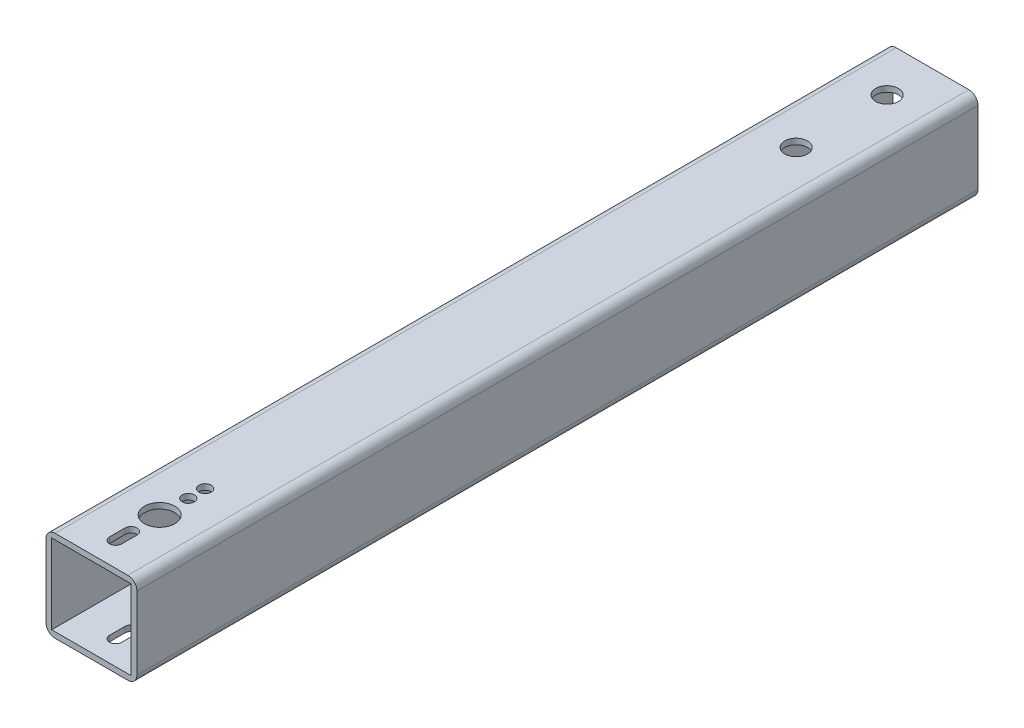
SolidWorks part; units mm, degrees
ref_plane "Front Plane" through (0, 0, 0) normal (0, 0, 1) x (1, 0, 0)
ref_plane "Top Plane" through (0, 0, 0) normal (0, 1, 0) x (1, 0, 0)
ref_plane "Right Plane" through (0, 0, 0) normal (1, 0, 0) x (0, 0, -1)
sketch "Sketch1" plane through (0, 0, 0) normal (0, 0, 1) x (1, 0, 0)
  line L1 (-24.2596, 11.4248) -> (1.1404, 11.4248)
  line L2 (-24.2596, 11.4248) -> (-24.2596, -13.9752)
  line L3 (-24.2596, -13.9752) -> (1.1404, -13.9752)
  line L4 (1.1404, 11.4248) -> (1.1404, -13.9752)
  line L5 (-22.6721, 9.8373) -> (-0.4471, 9.8373)
  line L6 (-22.6721, 9.8373) -> (-22.6721, -12.3877)
  line L7 (-22.6721, -12.3877) -> (-0.4471, -12.3877)
  line L8 (-0.4471, 9.8373) -> (-0.4471, -12.3877)
  dimension "D1" = 25.4
  dimension "D2" = 25.4
  dimension "D3" = 1.5875
  dimension "D4" = 1.5875
  dimension "D5" = 1.5875
  dimension "D6" = 1.5875
extrude "Boss-Extrude1" add sketch "Sketch1" along normal blind 234.95
fillet "Fillet1" radius 2.54 4 edges at (1.1404, -13.9752, 117.475) (-24.2596, -13.9752, 117.475) (-24.2596, 11.4248, 117.475) (1.1404, 11.4248, 117.475)
sketch "Sketch2" plane through (0, 11.4248, 0) normal (0, 1, 0) x (1, 0, 0)
  line L0 (-1.3996, 0) -> (-21.7196, 0) construction
  line L1 (0, 0) -> (0, -59.7417) construction
  line L2 (-11.5596, -12.7) -> (-11.5596, 0) construction
  line L3 (-1.3996, -234.95) -> (-1.3996, 0) construction
  line L4 (-21.7196, -50.8) -> (29.3119, -50.8) construction
  line L5 (-21.7196, 0) -> (-21.7196, -234.95) construction
  circle A0 centre (-11.5596, -12.7) radius 3.175
  circle A2 centre (-11.5596, -38.1) radius 3.175
  dimension "D1" = 6.35
  dimension "D2" = 12.7
  dimension "D3" = 6.35
  dimension "D4" = 50.8
  dimension "D6" = 25.4
extrude "Cut-Extrude1" cut sketch "Sketch2" against normal through all
sketch "Sketch3" plane through (0, 11.4248, 0) normal (0, 1, 0) x (1, 0, 0)
  line L0 (-11.5596, -215.9) -> (-15.3182, -190.7796) construction
  line L1 (-11.5596, -215.9) -> (13.426, -212.1616) construction
  line L2 (-11.5596, -215.9) -> (-29.2422, -202.8202) construction
  line L3 (-11.5596, -215.9) -> (-11.5596, -196.7728) construction
  line L5 (-11.5596, -223.9) -> (-11.5596, -228.195) construction
  line L6 (-9.8596, -223.9) -> (-9.8596, -228.195)
  line L7 (-13.2596, -223.9) -> (-13.2596, -228.195)
  line L8 (-11.5596, -207.9) -> (-11.5596, -223.9) construction
  line L11 (-11.5596, -215.9) -> (30.1254, -215.9) construction
  line L12 (-37.8321, -50.8) -> (104.3326, -50.8) construction
  line L13 (-1.3996, 0) -> (-21.7196, 0) construction
  circle A0 centre (-11.5596, -207.9) radius 1.7
  circle A1 centre (-11.5596, -203.195) radius 1.7
  circle A2 centre (-11.5596, -215.9) radius 20.9 construction
  circle A3 centre (-11.5596, -215.9) radius 4.25
  arc A6 (-9.8596, -223.9) -> (-13.2596, -223.9) centre (-11.5596, -223.9) ccw
  arc A7 (-13.2596, -228.195) -> (-9.8596, -228.195) centre (-11.5596, -228.195) ccw
  point P15 (0, 0)
  point P16 (-11.5864, -215.7207)
  point P17 (-11.5596, -196.9907)
  point P21 (-11.5596, -226.0475)
  point P33 (-11.5596, 0)
  dimension "D1" = 215.9
  dimension "D2" = 3.4
  dimension "D3" = 3.4
  dimension "D4" = 8.5
  dimension "D13" = 41.8
  dimension "D6" = 3.4
  dimension "D7" = 16
  dimension "D8" = 25
  dimension "D10" = 8
  dimension "D14" = 50.8
extrude "Cut-Extrude2" cut sketch "Sketch3" against normal through all and the other way through all
